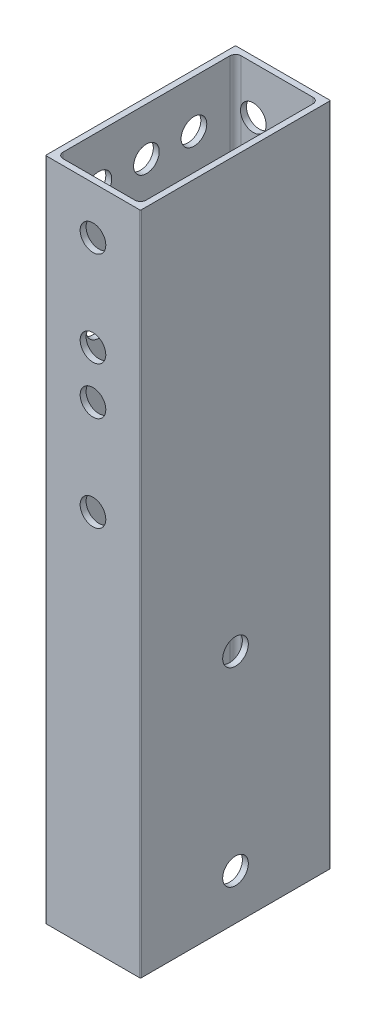
SolidWorks part; units mm, degrees
material "6061-T6 (SS)"
ref_plane "Front Plane" through (0, 0, 0) normal (0, 0, 1) x (1, 0, 0)
ref_plane "Top Plane" through (0, 0, 0) normal (0, 1, 0) x (1, 0, 0)
ref_plane "Right Plane" through (0, 0, 0) normal (1, 0, 0) x (0, 0, -1)
sketch "Sketch1" plane through (0, 0, 0) normal (0, 1, 0) x (1, 0, 0)
  line L0 (0.254, 50.8) -> (25.146, 50.8)
  line L1 (25.4, 50.546) -> (25.4, 0.254)
  line L2 (25.146, 0) -> (0.254, 0)
  line L3 (0, 0.254) -> (0, 50.546)
  line L4 (1.5875, 3.1115) -> (1.5875, 47.6885)
  line L5 (3.1115, 49.2125) -> (22.2885, 49.2125)
  line L6 (23.8125, 47.6885) -> (23.8125, 3.1115)
  line L7 (22.2885, 1.5875) -> (3.1115, 1.5875)
  line L8 (1.5875, 0.254) -> (1.5875, 50.546) construction
  line L9 (0.254, 49.2125) -> (25.146, 49.2125) construction
  line L10 (23.8125, 50.546) -> (23.8125, 0.254) construction
  line L11 (25.146, 1.5875) -> (0.254, 1.5875) construction
  arc A0 (0.254, 0) -> (0, 0.254) centre (0.254, 0.254) cw
  arc A1 (25.4, 0.254) -> (25.146, 0) centre (25.146, 0.254) cw
  arc A2 (25.146, 50.8) -> (25.4, 50.546) centre (25.146, 50.546) cw
  arc A3 (0.254, 50.8) -> (0, 50.546) centre (0.254, 50.546) ccw
  arc A4 (1.5875, 3.1115) -> (3.1115, 1.5875) centre (3.1115, 3.1115) ccw
  arc A5 (22.2885, 1.5875) -> (23.8125, 3.1115) centre (22.2885, 3.1115) ccw
  arc A6 (23.8125, 47.6885) -> (22.2885, 49.2125) centre (22.2885, 47.6885) ccw
  arc A7 (1.5875, 47.6885) -> (3.1115, 49.2125) centre (3.1115, 47.6885) cw
  point P8 (0, 0)
  point P11 (25.4, 0)
  point P14 (25.4, 50.8)
  point P17 (0, 50.8)
  dimension "D3" = 0.254
  dimension "D5" = 1.524
  dimension "D1" = 25.4
  dimension "D2" = 50.8
  dimension "D4" = 1.5875
extrude "Boss-Extrude1" add sketch "Sketch1" along normal blind 177.8
sketch "Sketch2" plane through (0, 0, 0) normal (-1, 0, 0) x (0, 0, 1)
  line L0 (-25.4, 0) -> (-25.4, 177.8) construction
  line L1 (-50.546, 0) -> (-0.254, 0) construction
  line L2 (-50.546, 177.8) -> (-0.254, 177.8) construction
  line L3 (-50.546, 177.8) -> (-50.546, 0) construction
  circle A0 centre (-25.4, 12.192) radius 10.16
  circle A1 centre (-25.4, 12.192) radius 3.429
  circle A2 centre (-25.4, 62.992) radius 10.16
  circle A3 centre (-25.4, 62.992) radius 3.429
  circle A4 centre (-38.1, 165.1) radius 3.429
  circle A5 centre (-25.4, 165.1) radius 3.429
  circle A6 centre (-12.7, 165.1) radius 3.429
  circle A7 centre (-25.4, 133.35) radius 3.429
  circle A8 centre (-12.7, 133.35) radius 3.429
  circle A9 centre (-25.4, 101.6) radius 3.429
  circle A10 centre (-12.7, 101.6) radius 3.429
  circle A11 centre (-38.1, 133.35) radius 3.429
  circle A12 centre (-38.1, 101.6) radius 3.429
  dimension "D1" = 20.32
  dimension "D2" = 6.858
  dimension "D6" = 12.446
  dimension "D3" = 12.192
  dimension "D5" = 50.8
  dimension "D7" = 12.7
  dimension "D10" = 31.75
  dimension "D11" = 12.7
  dimension "D4" = 2
  dimension "D8" = 3
  dimension "D9" = 3
extrude "Cut-Extrude1" cut sketch "Sketch2" against normal blind 12.7
extrude "Cut-Extrude2" cut sketch "Sketch2<3>" against normal through all contours L0 A3 | A3 L0 | L0 A1 | A1 L0 region at (0, 12.192, -26.8553) region at (0, 12.192, -23.9447) region at (0, 62.992, -26.8553) region at (0, 62.992, -23.9447)
sketch "Sketch2<3>" plane through (0, 0, 0) normal (-1, 0, 0) x (0, 0, 1) same geometry as "Sketch2"
sketch "Sketch3" plane through (0, 0, 0) normal (0, 0, 1) x (1, 0, 0)
  line L0 (25.146, 177.8) -> (25.146, 0) construction
  line L1 (0.254, 177.8) -> (25.146, 177.8) construction
  circle A0 centre (19.05, 165.1) radius 3.429
  circle A1 centre (6.35, 165.1) radius 3.429
  circle A2 centre (6.35, 133.35) radius 3.429
  circle A3 centre (6.35, 101.6) radius 3.429
  circle A4 centre (19.05, 133.35) radius 3.429
  circle A5 centre (19.05, 101.6) radius 3.429
  dimension "D1" = 6.858
  dimension "D2" = 6.096
  dimension "D3" = 12.7
  dimension "D6" = 12.7
  dimension "D7" = 31.75
  dimension "D4" = 2
  dimension "D5" = 3
extrude "Cut-Extrude3" cut sketch "Sketch3" against normal through all from surface starting at face at (12.7, 88.9, -1.5875)
sketch "Sketch4" plane through (0, 0, 0) normal (0, 0, 1) x (1, 0, 0)
  line L0 (12.7, 177.8) -> (12.7, 101.6) construction
  line L1 (0.254, 177.8) -> (25.146, 177.8) construction
  circle A0 centre (12.7, 165.1) radius 3.429
  circle A1 centre (12.7, 139.7) radius 3.429
  circle A2 centre (12.7, 101.6) radius 3.429
  circle A3 centre (12.7, 127) radius 3.429
  dimension "D1" = 6.858
  dimension "D3" = 25.4
  dimension "D4" = 12.7
  dimension "D5" = 25.4
  dimension "D2" = 12.7
extrude "Cut-Extrude4" cut sketch "Sketch4" against normal blind 2.54
